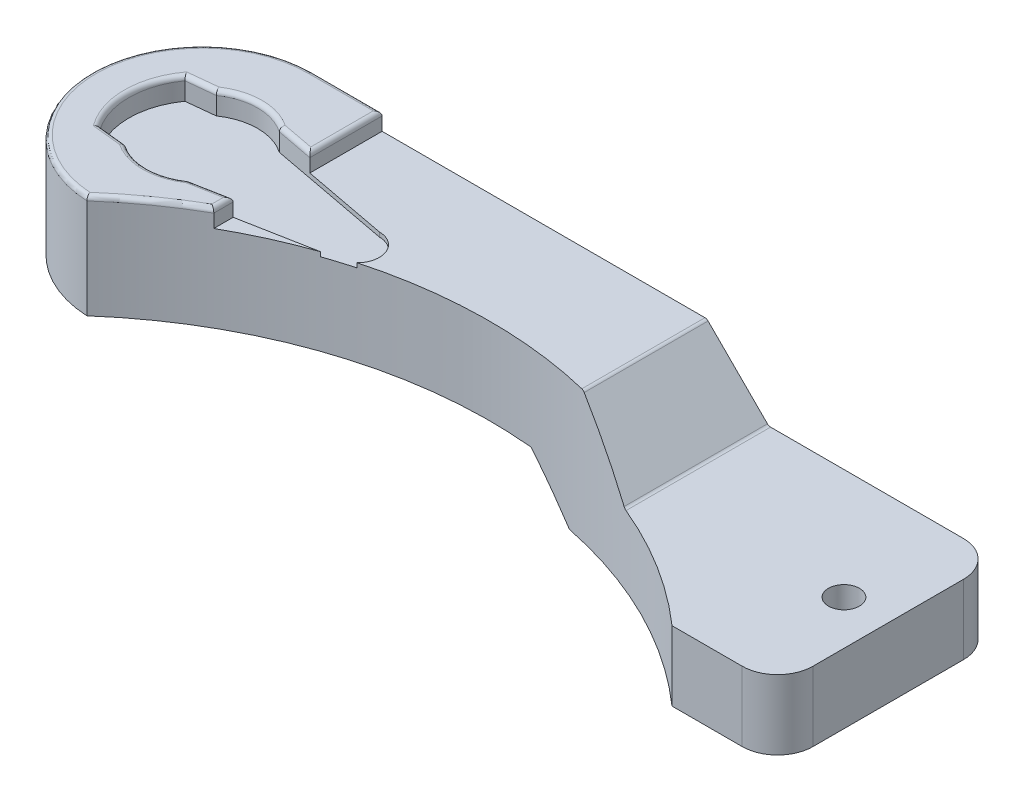
SolidWorks part; units mm, degrees
ref_plane "Front Plane" through (0, 0, 0) normal (0, 0, 1) x (1, 0, 0)
ref_plane "Top Plane" through (0, 0, 0) normal (0, 1, 0) x (1, 0, 0)
ref_plane "Right Plane" through (0, 0, 0) normal (1, 0, 0) x (0, 0, -1)
sketch "Sketch1" plane through (0, 0, 0) normal (0, 1, 0) x (1, 0, 0)
  line L1 (-45, 12.5) -> (45, 12.5)
  line L2 (-45, 12.5) -> (-45, -12.5)
  line L3 (-45, -12.5) -> (45, -12.5)
  line L4 (45, 12.5) -> (45, -12.5)
  dimension "D1" = 90
  dimension "D2" = 45
  dimension "D3" = 25
  dimension "D4" = 12.5
extrude "Boss-Extrude1" add sketch "Sketch1" along normal blind 16.87
sketch "Sketch3" plane through (0, 16.87, 0) normal (0, 1, 0) x (1, 0, 0)
  line L0 (-39.2721, 4.7988) -> (-36.061, 5.1363)
  line L5 (-45, 12.5) -> (-45, -12.5) construction
  line L6 (-45, -12.5) -> (45, -12.5) construction
  line L7 (-39.2721, -4.7988) -> (-36.061, -5.1363)
  line L9 (-28.939, 5.1363) -> (-15, 2.5)
  line L11 (-28.939, -5.1363) -> (-15, -2.5)
  arc A0 (-28.939, 5.1363) -> (-36.061, 5.1363) centre (-32.5, 0) ccw
  arc A1 (-15, -2.5) -> (-15, 2.5) centre (-15, 0) ccw
  arc A3 (-36.061, -5.1363) -> (-28.939, -5.1363) centre (-32.5, 0) ccw
  arc A4 (-39.2721, -4.7988) -> (-39.2721, 4.7988) centre (-32.5, 0) cw
  point P5 (-40.8, 0)
  dimension "D1" = 12.5
  dimension "D2" = 5
  dimension "D3" = 3.2111
  dimension "D14" = 8.3
  dimension "D4" = 3.2111
  dimension "D5" = 17.5
  dimension "D6" = 12.5
  dimension "D7" = 12.5
  dimension "D8" = 12.5
  dimension "D9" = 6.7721
  dimension "D10" = 6.7721
  dimension "D11" = 13.939
  dimension "D12" = 13.939
extrude "Cut-Extrude2" cut sketch "Sketch3" against normal blind 2.5
sketch "Esquisse2" plane through (0, 0, 12.5) normal (0, 0, 1) x (1, 0, 0)
  line L0 (10, 16.87) -> (19, 7.87)
  line L1 (45, 16.87) -> (10, 16.87)
  line L2 (45, 16.87) -> (45, 7.87)
  line L3 (45, 7.87) -> (10, 7.87)
  line L4 (10, 16.87) -> (10, 7.87)
  line L5 (-45, 0) -> (10, 0)
  line L8 (10, 0) -> (10, 7.87)
  line L9 (10, 0) -> (4.88, 5.12)
  line L10 (4.88, 5.12) -> (-45, 5.12)
  line L11 (-45, 5.12) -> (-45, 0)
  line M3 (-45, 0) -> (45, 0)
  line M4 (45, 0) -> (45, 16.87)
  line M5 (45, 16.87) -> (-45, 16.87)
  line M6 (-45, 16.87) -> (-45, 0)
  dimension "D1" = 35
  dimension "D2" = 9
  dimension "D3" = 45
  dimension "D4" = 45
  dimension "D5" = 2.75
extrude "Enlèv. mat.-Extru.1" cut sketch "Esquisse2" against normal blind 34 contours L8 M3 M6 | L4 L3 M5 M4 region at (29.6393, 12.5913, 12.5) region at (-18.7592, 2.5183, 12.5)
fillet "Fillet1" 2 edges at (-45, 10.995, 12.5) (-45, 10.995, -12.5) type full round first side face at (5.485, 7.465, 12.5) second side face at (5.485, 7.465, -12.5) middle face at (-45, 10.995, 0)
sketch "Esquisse5" plane through (0, 0, 0) normal (0, -1, 0) x (-1, 0, 0)
  line L0 (-45, -12.5) -> (-45, 12.5) construction
  circle A0 centre (-40, 0) radius 1.75
  dimension "D2" = 3.5
  dimension "D1" = 5
extrude "Enlèv. mat.-Extru.4" cut sketch "Esquisse5" against normal through all
fillet "Fillet3" radius 4 2 edges at (45, 3.935, -12.5) (45, 3.935, 12.5)
sketch "Sketch8" plane through (0, 16.87, 0) normal (0, 1, 0) x (1, 0, 0)
  line L1 (-24.6881, 14.1476) -> (13.3414, 14.1476)
  line L2 (-24.6881, 14.1476) -> (-24.6881, -6.796)
  line L3 (-24.6881, -6.796) -> (13.3414, -6.796)
  line L4 (13.3414, 14.1476) -> (13.3414, -6.796)
  dimension "D1" = 38.0295
  dimension "D2" = 20.9436
  dimension "D3" = 14.1476
  dimension "D4" = 24.6881
extrude "Cut-Extrude6" cut sketch "Sketch8" against normal blind 2
sketch "Esquisse17" plane through (0, 5.12, 0) normal (0, -1, 0) x (1, 0, 0)
  circle A0 centre (-32.5, 0) radius 6.45
  dimension "D1" = 12.9
extrude "Enlèv. mat.-Extru.7" cut sketch "Esquisse17" against normal blind 3.6
sketch "Esquisse18" plane through (0, 0, 0) normal (0, 1, 0) x (1, 0, 0)
  circle A0 centre (0, -50) radius 50
  dimension "D2" = 100
  dimension "D1" = 50
extrude "Enlèv. mat.-Extru.8" cut sketch "Esquisse18" against normal through all and the other way through all
fillet "Fillet4" radius 0.5 14 edges at (-28.5941, 16.87, -12.5) (19, 7.87, -4.3747) (12, 14.87, -5.5193) (-37.6665, 16.87, -4.9676) (-26.8136, 16.87, -4.7343) (-32.5, 16.87, -6.25) (-37.6665, 16.87, 4.9676) (-24.6881, 16.87, 5.4262) (-26.8136, 16.87, 4.7343) (-32.5, 16.87, 6.25) (-40.8, 16.87, 0) (-24.6881, 16.87, -8.4162) (-29.0267, 16.87, 9.2882) (-44.9969, 16.87, -0.279)
